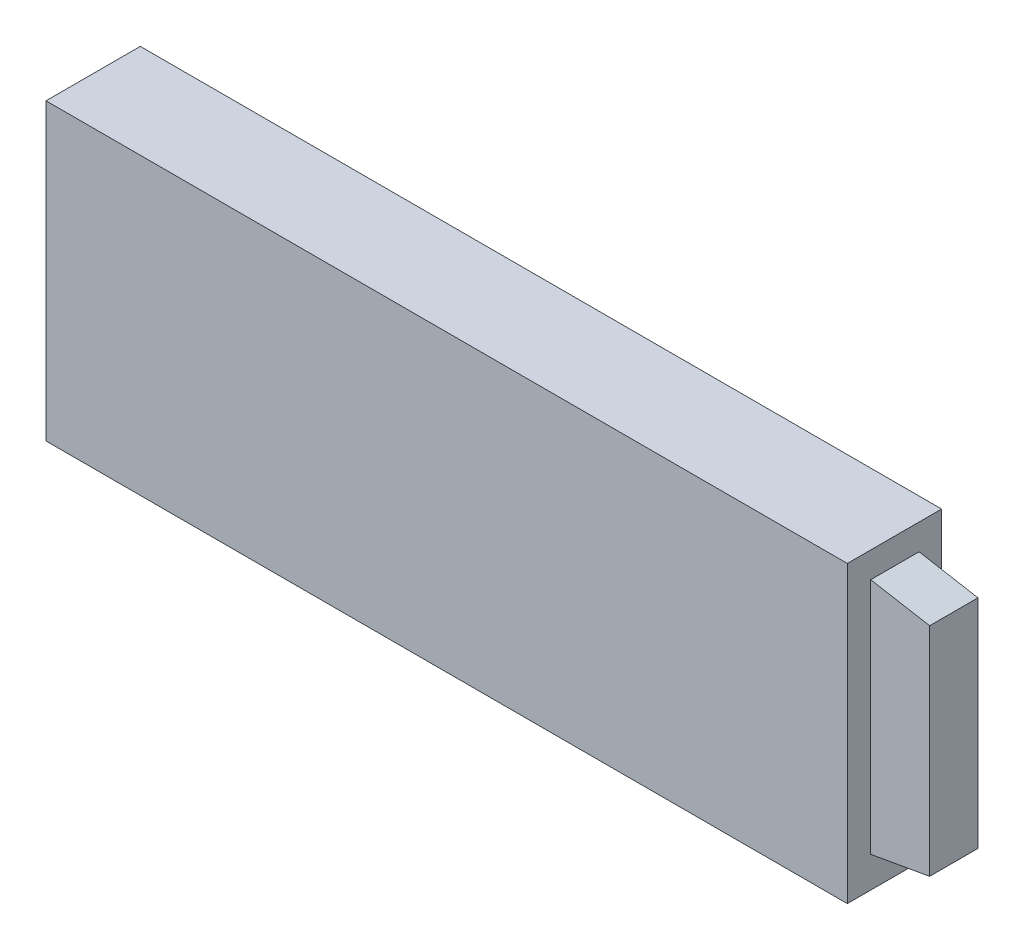
SolidWorks part; units mm, degrees
ref_plane "Front Plane" through (0, 0, 0) normal (0, 0, 1) x (1, 0, 0)
ref_plane "Top Plane" through (0, 0, 0) normal (0, 1, 0) x (1, 0, 0)
ref_plane "Right Plane" through (0, 0, 0) normal (1, 0, 0) x (0, 0, -1)
sketch "Sketch1" plane through (0, 0, 0) normal (0, 0, -1) x (1, 0, 0)
  line L1 (0, 0) -> (68, 0)
  line L2 (0, 0) -> (0, 25)
  line L3 (0, 25) -> (68, 25)
  line L4 (68, 0) -> (68, 25)
  dimension "D1" = 68
  dimension "D2" = 25
extrude "Boss-Extrude1" add sketch "Sketch1" along normal blind 8 contours L1 L4 L3 L2
sketch "Sketch13" plane through (68, 0, 0) normal (1, 0, 0) x (0, 0, -1)
  line L1 (1.9856, -2.1877) -> (6.0883, -2.1877)
  line L2 (1.9856, -2.1877) -> (1.9856, -22.3687)
  line L3 (1.9856, -22.3687) -> (6.0883, -22.3687)
  line L4 (6.0883, -2.1877) -> (6.0883, -22.3687)
extrude "Boss-Extrude5" add sketch "Sketch13" along normal blind 5
chamfer "Chamfer1" distance 5 angle 10 1 edges at (73, -2.1877, -4.037) first distance on face at (70.5, -2.1877, -4.037)
chamfer "Chamfer2" distance 5 angle 10 1 edges at (73, -22.3687, -4.037) first distance on face at (70.5, -22.3687, -4.037)
sketch "Sketch14" plane through (0, 0, -8) normal (0, 0, -1) x (-1, 0, 0)
  line L0 (133.5484, 577.3308) -> (933.5484, 577.3308) construction
  line L1 (-222.4325, 95.2462) -> (-222.4325, 507.2462) construction
